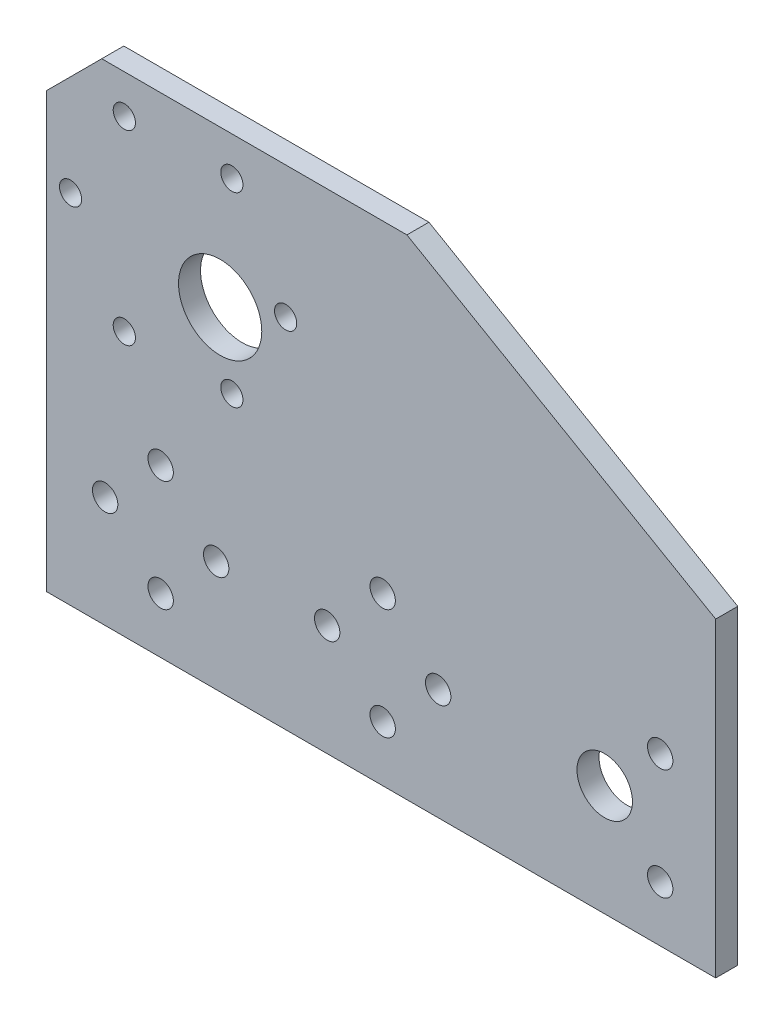
SolidWorks part; units mm, degrees
note: '?' marks a value the reader was unsure of.
material "6061-T6 (SS)"
ref_plane "Front" through (0, 0, 0) normal (0, 0, 1) x (1, 0, 0)
ref_plane "Top" through (0, 0, 0) normal (0, 1, 0) x (1, 0, 0)
ref_plane "Right" through (0, 0, 0) normal (1, 0, 0) x (0, 0, -1)
ref_axis "side-side" through (80.9, 0, 0) along (-1, 0, 0)?
ref_axis "up-down" through (0, 50, 0) along (0, -1, 0)?
ref_axis "front-back" through (0, 0, -80.9) along (0, 0, 1)?
sketch "Sketch1" plane through (0, 0, 0) normal (0, 0, 1) x (1, 0, 0)
  line L1 (16, -16) -> (-80.4878, -16)
  line L3 (16, 28.8038) -> (16, -16)
  line L4 (-80.4878, -16) -> (-80.4878, 46.5)
  line L5 (16, 28.8038) -> (-28.5071, 54.5)
  line L6 (-28.5071, 54.5) -> (-72.4878, 54.5)
  line L7 (0, 0) -> (-61.4878, 35.5) construction
  line L8 (-72.4878, 54.5) -> (-80.4878, 46.5)
  circle A1 centre (0, 0) radius 4
  circle A5 centre (-69.2378, 48.9234) radius 1.25 construction
  circle A7 centre (-53.7378, 48.9234) radius 1.25 construction
  circle A9 centre (-76.9878, 35.5) radius 1.25 construction
  circle A11 centre (-69.2378, 22.0766) radius 1.25 construction
  circle A13 centre (-53.7378, 22.0766) radius 1.25 construction
  circle A15 centre (-45.9878, 35.5) radius 1.25 construction
  circle A17 centre (-55.4256, 32) radius 6 construction
  dimension "D1" = 8
  dimension "D2" = 8
extrude "Boss-Extrude1" add sketch "Sketch1" against normal blind 3.175
sketch "Sketch2" plane through (0, 0, 0) normal (0, 0, 1) x (1, 0, 0)
  circle A3 centre (-8, 0) radius 1.3525 construction
  circle A5 centre (0, 8) radius 1.3525 construction
hole_wizard "M3 Clearance Hole1" positions "Sketch3" profile "Sketch4" hole size "M3" standard "ANSI Metric" end condition through all
sketch "Sketch3" plane through (0, 0, 0) normal (0, 0, 1) x (1, 0, 0)
  point P0 (-69.2378, 48.9234)
  point P3 (-53.7378, 48.9234)
  point P6 (-45.9878, 35.5)
  point P9 (-53.7378, 22.0766)
  point P12 (-69.2378, 22.0766)
  point P15 (-76.9878, 35.5)
sketch "Sketch4" plane through (-69.2378, 48.9234, 0) normal (1, 0, 0) x (0, -1, 0)
  line L0 (0, 0) -> (0, 3.175)
  line L1 (0, 3.175) -> (1.6, 3.175)
  line L2 (1.6, 3.175) -> (1.6, 0)
  line L5 (1.6, 0) -> (0, 0)
  line L11 (0, -6.35) -> (0, 107.95) construction
  dimension "Thru Hole Dia." = 3.2
  dimension "Thru Hole Depth" = 3.175
hole_wizard "Ø12.0 (12) Diameter Hole1" positions "Sketch5" profile "Sketch6" hole size "Ø12.0" standard "ANSI Metric" end condition through all
sketch "Sketch5" plane through (0, 0, 0) normal (0, 0, 1) x (1, 0, 0)
  point P0 (-55.4256, 32)
sketch "Sketch6" plane through (-55.4256, 32, 0) normal (1, 0, 0) x (0, -1, 0)
  line L0 (0, 0) -> (0, 3.175)
  line L1 (0, 3.175) -> (6, 3.175)
  line L2 (6, 3.175) -> (6, 0)
  line L5 (6, 0) -> (0, 0)
  line L11 (0, -6.35) -> (0, 107.95) construction
  dimension "Thru Hole Dia." = 12
  dimension "Thru Hole Depth" = 3.175
hole_wizard "#6 Clearance Hole3" [suppressed] positions "Sketch7" profile "Sketch8" hole size "#6" standard "ANSI Inch"
sketch "Sketch7" plane through (0, 0, 0) normal (0, 0, 1) x (1, 0, 0)
  circle A0 centre (0, 0) radius 8 construction
  point P0 (0, 8)
  point P3 (-8, 0)
  point P10 (0, -8)
  point P12 (8, 0)
sketch "Sketch8" plane through (0, 8, 0) normal (1, 0, 0) x (0, -1, 0)
  line L0 (0, 0) -> (0, 3.175)
  line L1 (0, 3.175) -> (1.8288, 3.175)
  line L2 (1.8288, 3.175) -> (1.8288, 0)
  line L5 (1.8288, 0) -> (0, 0)
  line L11 (0, -6.35) -> (0, 107.95) construction
  dimension "Thru Hole Dia." = 3.6576
  dimension "Thru Hole Depth" = 3.175
hole_wizard "#6 Clearance Hole2" positions "Sketch9" profile "Sketch11" hole size "#6" standard "ANSI Inch" end condition through all
sketch "Sketch9" plane through (0, 0, 0) normal (0, 0, 1) x (1, 0, 0)
  line L0 (-32, 8) -> (0, 8) construction
  circle A0 centre (-32, 0) radius 8 construction
  circle A1 centre (-64, 0) radius 8 construction
  point P10 (-32, -8)
  point P25 (-64, -8)
  point P27 (-72, 0)
  dimension "D1" = 32
  dimension "D2" = 32
sketch "Sketch11" plane through (-72, 0, 0) normal (1, 0, 0) x (0, -1, 0)
  line L0 (0, 0) -> (0, 3.175)
  line L1 (0, 3.175) -> (1.8288, 3.175)
  line L2 (1.8288, 3.175) -> (1.8288, 0)
  line L5 (1.8288, 0) -> (0, 0)
  line L11 (0, -6.35) -> (0, 107.95) construction
  dimension "Thru Hole Dia." = 3.6576
  dimension "Thru Hole Depth" = 3.175
hole_wizard "#6 Clearance Hole1" positions "Sketch12" profile "Sketch13" hole size "#6" standard "ANSI Inch" end condition through all
sketch "Sketch12" plane through (0, 0, 0) normal (0, 0, 1) x (1, 0, 0)
  circle A0 centre (-32, 0) radius 8 construction
  circle A1 centre (-64, 0) radius 8 construction
  point P0 (-32, 8)
  point P3 (-24, 0)
  point P7 (-64, 8)
  point P11 (-56, 0)
  point P20 (-40, 0)
  point P24 (8, 8)
  point P26 (8, -8)
sketch "Sketch13" plane through (-32, 8, 0) normal (1, 0, 0) x (0, -1, 0)
  line L0 (0, 0) -> (0, 3.175)
  line L1 (0, 3.175) -> (1.8288, 3.175)
  line L2 (1.8288, 3.175) -> (1.8288, 0)
  line L5 (1.8288, 0) -> (0, 0)
  line L11 (0, -6.35) -> (0, 107.95) construction
  dimension "Thru Hole Dia." = 3.6576
  dimension "Thru Hole Depth" = 3.175
